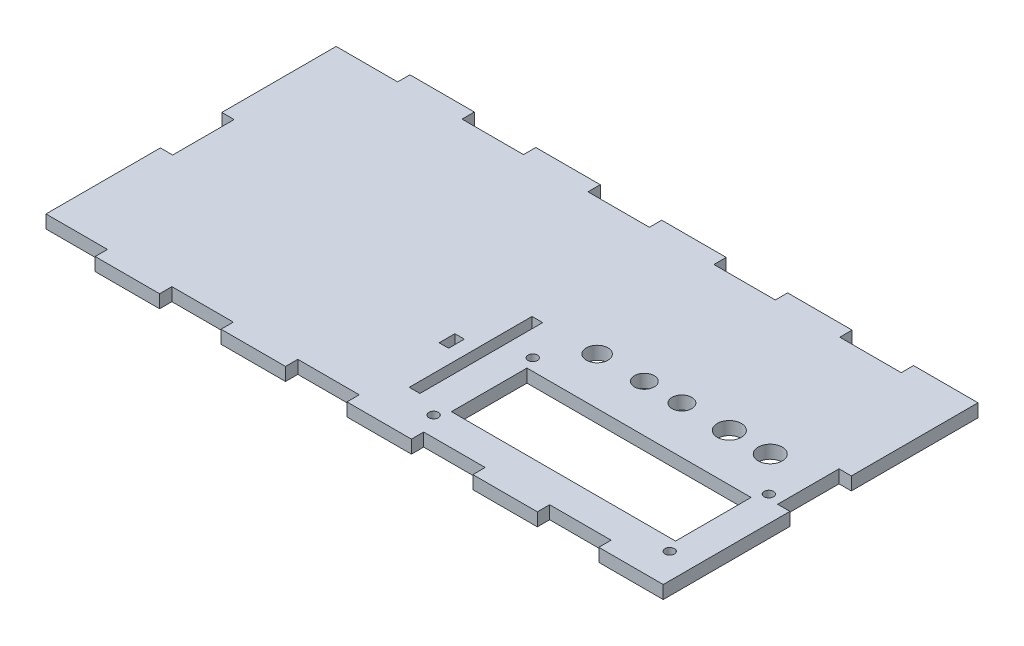
SolidWorks part; units mm, degrees
ref_plane "Front Plane" through (0, 0, 0) normal (0, 0, 1) x (1, 0, 0)
ref_plane "Top Plane" through (0, 0, 0) normal (0, 1, 0) x (1, 0, 0)
ref_plane "Right Plane" through (0, 0, 0) normal (1, 0, 0) x (0, 0, -1)
sketch "Sketch1" plane through (0, 0, 0) normal (0, 1, 0) x (1, 0, 0)
  line L1 (-100, 50) -> (100, 50)
  line L2 (-100, 50) -> (-100, -50)
  line L3 (-100, -50) -> (100, -50)
  line L4 (100, 50) -> (100, -50)
  line L5 (-100, 50) -> (100, -50) construction
  line L6 (-100, -50) -> (100, 50) construction
  point P0 (0, 0)
  dimension "Length" = 200
  dimension "with" = 100
extrude "Boss-Extrude1" add sketch "Sketch1" along normal blind 4.15
sketch "Sketch3" plane through (0, 4.15, 0) normal (0, 1, 0) x (1, 0, 0)
  line L0 (-100, 46.09) -> (-100, 50)
  line L1 (-100, -50) -> (-80.48, -50)
  line L2 (-100, -50) -> (-100, -46.09)
  line L3 (-100, -46.09) -> (-80.48, -46.09)
  line L4 (-80.48, -50) -> (-80.48, -46.09)
  line L5 (-100, 46.09) -> (-80.48, 46.09)
  line L6 (-80.48, 46.09) -> (-80.48, 50)
  line L7 (-100, 50) -> (-80.48, 50)
  line L8 (-60, 46.09) -> (-60, 50)
  line L9 (-60, 46.09) -> (-40.48, 46.09)
  line L10 (-40.48, 46.09) -> (-40.48, 50)
  line L11 (-60, 50) -> (-40.48, 50)
  line L12 (-20, 46.09) -> (-20, 50)
  line L13 (-20, 46.09) -> (-0.48, 46.09)
  line L14 (-0.48, 46.09) -> (-0.48, 50)
  line L15 (-20, 50) -> (-0.48, 50)
  line L16 (20, 46.09) -> (20, 50)
  line L17 (20, 46.09) -> (39.52, 46.09)
  line L18 (39.52, 46.09) -> (39.52, 50)
  line L19 (20, 50) -> (39.52, 50)
  line L20 (60, 46.09) -> (60, 50)
  line L21 (60, 46.09) -> (79.52, 46.09)
  line L22 (79.52, 46.09) -> (79.52, 50)
  line L23 (60, 50) -> (79.52, 50)
  line L24 (-60, -50) -> (-60, -46.09)
  line L25 (-60, -50) -> (-40.48, -50)
  line L26 (-40.48, -50) -> (-40.48, -46.09)
  line L27 (-60, -46.09) -> (-40.48, -46.09)
  line L28 (-20, -50) -> (-20, -46.09)
  line L29 (-20, -50) -> (-0.48, -50)
  line L30 (-0.48, -50) -> (-0.48, -46.09)
  line L31 (-20, -46.09) -> (-0.48, -46.09)
  line L32 (20, -50) -> (20, -46.09)
  line L33 (20, -50) -> (39.52, -50)
  line L34 (39.52, -50) -> (39.52, -46.09)
  line L35 (20, -46.09) -> (39.52, -46.09)
  line L36 (60, -50) -> (60, -46.09)
  line L37 (60, -50) -> (79.52, -50)
  line L38 (79.52, -50) -> (79.52, -46.09)
  line L39 (60, -46.09) -> (79.52, -46.09)
  line L40 (-100, -50) -> (100, -50) construction
  line L41 (100, 50) -> (-100, 50) construction
  point P5 (-80.48, -48.045)
  dimension "D1" = 3.91
  dimension "D2" = 19.52
  dimension "D5" = 20.48
  dimension "D3" = 2
  dimension "D4" = 5
extrude "Cut-Extrude2" cut sketch "Sketch3" against normal blind 10
sketch "Sketch4" plane through (0, 4.15, 0) normal (0, 1, 0) x (1, 0, 0)
  line L0 (-100, 9.76) -> (-100, -9.76)
  line L1 (-100, 9.76) -> (-96.09, 9.76)
  line L2 (-100, -9.76) -> (-96.09, -9.76)
  line L3 (-96.09, 9.76) -> (-96.09, -9.76)
  line L4 (-100, 46.09) -> (-100, -46.09) construction
  line L5 (0, -2.2825) -> (0, 2.2825) construction
  line L6 (100, -9.76) -> (96.09, -9.76)
  line L7 (96.09, 9.76) -> (96.09, -9.76)
  line L8 (100, 9.76) -> (96.09, 9.76)
  line L9 (100, 9.76) -> (100, -9.76)
  point P6 (-100, 0)
  dimension "D1" = 19.52
  dimension "D2" = 3.91
extrude "Cut-Extrude3" cut sketch "Sketch4" against normal blind 10
sketch "Sketch5" [suppressed] plane through (0, 4.15, 0) normal (0, 1, 0) x (1, 0, 0)
  line L0 (100, -36.09) -> (100, -40)
  line L1 (100, -36.09) -> (80.48, -36.09)
  line L2 (100, -40) -> (80.48, -40)
  line L3 (80.48, -36.09) -> (80.48, -40)
  line L4 (100, -40) -> (100, -9.76) construction
  line L5 (60, -36.09) -> (60, -40)
  line L6 (60, -36.09) -> (40.48, -36.09)
  line L7 (40.48, -36.09) -> (40.48, -40)
  line L8 (60, -40) -> (40.48, -40)
  line L9 (20, -36.09) -> (20, -40)
  line L10 (20, -36.09) -> (0.48, -36.09)
  line L11 (0.48, -36.09) -> (0.48, -40)
  line L12 (20, -40) -> (0.48, -40)
  line L13 (-20, -36.09) -> (-20, -40)
  line L14 (-20, -36.09) -> (-39.52, -36.09)
  line L15 (-39.52, -36.09) -> (-39.52, -40)
  line L16 (-20, -40) -> (-39.52, -40)
  line L17 (-60, -36.09) -> (-60, -40)
  line L18 (-60, -36.09) -> (-79.52, -36.09)
  line L19 (-79.52, -36.09) -> (-79.52, -40)
  line L20 (-60, -40) -> (-79.52, -40)
  line L21 (60, 40) -> (60, 36.09)
  line L22 (60, 40) -> (40.48, 40)
  line L23 (40.48, 40) -> (40.48, 36.09)
  line L24 (60, 36.09) -> (40.48, 36.09)
  line L25 (20, 40) -> (20, 36.09)
  line L26 (20, 40) -> (0.48, 40)
  line L27 (0.48, 40) -> (0.48, 36.09)
  line L28 (20, 36.09) -> (0.48, 36.09)
  line L29 (-20, 40) -> (-20, 36.09)
  line L30 (-20, 40) -> (-39.52, 40)
  line L31 (-39.52, 40) -> (-39.52, 36.09)
  line L32 (-20, 36.09) -> (-39.52, 36.09)
  line L33 (-60, 40) -> (-60, 36.09)
  line L34 (-60, 40) -> (-79.52, 40)
  line L35 (-79.52, 40) -> (-79.52, 36.09)
  line L36 (-60, 36.09) -> (-79.52, 36.09)
  line L37 (100, 40) -> (100, 36.09)
  line L38 (100, 40) -> (80.48, 40)
  line L39 (80.48, 40) -> (80.48, 36.09)
  line L40 (100, 36.09) -> (80.48, 36.09)
  line L41 (100, 40) -> (-100, 40) construction
  point P9 (100, 38.045)
  point P46 (100, -38.045)
  dimension "D1" = 3.91
  dimension "D2" = 19.52
  dimension "D5" = 20.48
  dimension "D3" = 5
  dimension "D4" = 2
extrude "Cut-Extrude4" [suppressed] cut sketch "Sketch5" against normal blind 10
sketch "Sketch6" [suppressed] plane through (0, 4.15, 0) normal (0, 1, 0) x (1, 0, 0)
  line L4 (-2.2825, 0) -> (2.2825, 0) construction
  line L5 (-40, -50) -> (-10.24, -50)
  line L6 (-40, -50) -> (-40, -46.09)
  line L7 (-40, -46.09) -> (-10.24, -46.09)
  line L8 (-10.24, -50) -> (-10.24, -46.09)
  line L9 (40, -50) -> (10.24, -50)
  line L10 (40, -50) -> (40, -46.09)
  line L11 (40, -46.09) -> (10.24, -46.09)
  line L12 (10.24, -50) -> (10.24, -46.09)
  line L13 (-40, 46.09) -> (-10.24, 46.09)
  line L14 (-10.24, 50) -> (-10.24, 46.09)
  line L15 (-40, 50) -> (-10.24, 50)
  line L16 (-40, 50) -> (-40, 46.09)
  line L17 (40, 46.09) -> (10.24, 46.09)
  line L18 (10.24, 50) -> (10.24, 46.09)
  line L19 (40, 50) -> (10.24, 50)
  line L20 (40, 50) -> (40, 46.09)
  line L21 (0, -2.2825) -> (0, 2.2825) construction
  line L22 (40, -46.09) -> (36.09, -46.09)
  line L23 (40, -46.09) -> (40, -10.24)
  line L24 (40, -10.24) -> (36.09, -10.24)
  line L25 (36.09, -46.09) -> (36.09, -10.24)
  line L26 (40, 46.09) -> (36.09, 46.09)
  line L27 (40, 46.09) -> (40, 10.24)
  line L28 (40, 10.24) -> (36.09, 10.24)
  line L29 (36.09, 46.09) -> (36.09, 10.24)
  line L30 (-40, 10.24) -> (-36.09, 10.24)
  line L31 (-36.09, 46.09) -> (-36.09, 10.24)
  line L32 (-40, 46.09) -> (-36.09, 46.09)
  line L33 (-40, 46.09) -> (-40, 10.24)
  line L34 (-40, -10.24) -> (-36.09, -10.24)
  line L35 (-36.09, -46.09) -> (-36.09, -10.24)
  line L36 (-40, -46.09) -> (-36.09, -46.09)
  line L37 (-40, -46.09) -> (-40, -10.24)
  dimension "D1" = 20.48
  dimension "D2" = 3.91
  dimension "D4" = 29.76
  dimension "D5" = 3.91
  dimension "D6" = 3.91
  dimension "D7" = 20.48
extrude "Cut-Extrude5" [suppressed] cut sketch "Sketch6" against normal blind 10
sketch "Sketch7" plane through (0, 4.15, 0) normal (0, 1, 0) x (1, 0, 0)
  line L0 (39.52, -46.09) -> (20, -46.09) construction
  line L1 (18.8, -36.09) -> (90, -36.09)
  line L2 (18.8, -36.09) -> (18.8, -12.09)
  line L3 (18.8, -12.09) -> (90, -12.09)
  line L4 (90, -36.09) -> (90, -12.09)
  line L5 (100, -50) -> (100, -9.76) construction
  dimension "D1" = 71.2
  dimension "D2" = 24
  dimension "D3" = 10
  dimension "D4" = 10
extrude "Cut-Extrude6" cut sketch "Sketch7" against normal blind 10
sketch "Sketch8" plane through (0, 4.15, 0) normal (0, 1, 0) x (1, 0, 0)
  line L0 (18.8, -12.09) -> (18.8, -36.09) construction
  line L1 (90, -36.09) -> (90, -12.09) construction
  line L4 (90, -12.09) -> (18.8, -12.09) construction
  line L5 (18.8, -36.09) -> (90, -36.09) construction
  circle A0 centre (16.9, -39.84) radius 1.5
  circle A1 centre (16.9, -8.34) radius 1.5
  circle A2 centre (91.9, -8.34) radius 1.5
  circle A3 centre (91.9, -39.84) radius 1.5
  dimension "D1" = 2
  dimension "D3" = 3
  dimension "D7" = 1.9
  dimension "D4" = 3.75
  dimension "D5" = 3.75
  dimension "D6" = 1.9
  dimension "D2" = 2
extrude "Cut-Extrude7" cut sketch "Sketch8" against normal blind 10
sketch "Sketch9" plane through (0, 4.15, 0) normal (0, 1, 0) x (1, 0, 0)
  line L0 (-0.48, -46.09) -> (-20, -46.09) construction
  line L1 (8.8, -36.09) -> (5.4, -36.09)
  line L2 (8.8, -36.09) -> (8.8, 2.91)
  line L3 (8.8, 2.91) -> (5.4, 2.91)
  line L4 (5.4, -36.09) -> (5.4, 2.91)
  line L5 (18.8, -12.09) -> (18.8, -36.09) construction
  dimension "D1" = 3.4
  dimension "D2" = 39
  dimension "D3" = 10
  dimension "D4" = 10
extrude "Cut-Extrude8" cut sketch "Sketch9" against normal blind 10
sketch "Sketch10" plane through (0, 4.15, 0) normal (0, 1, 0) x (1, 0, 0)
  line L0 (90, -12.09) -> (18.8, -12.09) construction
  line L1 (96.09, 9.76) -> (96.09, -9.76) construction
  circle A0 centre (26.09, 2.91) radius 3.425
  dimension "D1" = 6.85
  dimension "D2" = 15
  dimension "D3" = 70
extrude "Cut-Extrude9" cut sketch "Sketch10" against normal blind 10 contours A0
sketch "Sketch11" plane through (0, 4.15, 0) normal (0, 1, 0) x (1, 0, 0)
  line L0 (90, -12.09) -> (18.8, -12.09) construction
  line L1 (96.09, 9.76) -> (96.09, -9.76) construction
  circle A0 centre (41.09, 2.91) radius 3.125
  circle A1 centre (53.0309, 2.91) radius 3.125
  dimension "D1" = 6.25
  dimension "D3" = 55
  dimension "D2" = 15
  dimension "D4" = 2
extrude "Cut-Extrude10" cut sketch "Sketch11" against normal blind 10
sketch "Sketch12" plane through (0, 4.15, 0) normal (0, 1, 0) x (1, 0, 0)
  line L0 (90, -12.09) -> (18.8, -12.09) construction
  line L1 (96.09, 9.76) -> (96.09, -9.76) construction
  circle A0 centre (68.09, 2.91) radius 3.825
  circle A1 centre (81.09, 2.91) radius 3.825
  dimension "D1" = 7.65
  dimension "D2" = 15
  dimension "D4" = 28
  dimension "D5" = 15
  dimension "D3" = 2
extrude "Cut-Extrude11" cut sketch "Sketch12" against normal blind 10
sketch "Sketch13" [suppressed] plane through (0, 4.15, 0) normal (0, 1, 0) x (1, 0, 0)
  line L0 (100, -50) -> (100, 50) construction
  line L1 (24.76, 50) -> (-24.76, 50)
  line L3 (24.76, 45.78) -> (-24.76, 45.78)
  line L4 (-24.76, 50) -> (-24.76, 45.78)
  line L5 (0, -2.2825) -> (0, 2.2825) construction
  line L6 (-100, 50) -> (-50.24, 50)
  line L8 (-95.78, 45.78) -> (-50.24, 45.78)
  line L9 (-50.24, 50) -> (-50.24, 45.78)
  line L10 (95.78, 45.78) -> (50.24, 45.78)
  line L11 (50.24, 50) -> (50.24, 45.78)
  line L12 (100, 50) -> (50.24, 50)
  line L14 (24.76, 50) -> (24.76, 45.78)
  line L15 (-100, 50) -> (-100, -50) construction
  line L21 (-100, -15.72) -> (-100, 15.72)
  line L22 (-100, 15.72) -> (-95.78, 15.72)
  line L23 (-95.78, -15.72) -> (-95.78, 15.72)
  line L24 (-2.2825, 0) -> (2.2825, 0) construction
  line L26 (-100, 50) -> (-100, 30.24)
  line L27 (-100, 30.24) -> (-95.78, 30.24)
  line L28 (-95.78, 45.78) -> (-95.78, 30.24)
  line L29 (-100, -15.72) -> (-95.78, -15.72)
  line L30 (-100, -30.24) -> (-95.78, -30.24)
  line L31 (-95.78, -50) -> (-95.78, -30.24)
  line L32 (-100, -50) -> (-95.78, -50)
  line L33 (-100, -50) -> (-100, -30.24)
  line L34 (100, 30.24) -> (95.78, 30.24)
  line L35 (95.78, 45.78) -> (95.78, 30.24)
  line L37 (100, 50) -> (100, 30.24)
  line L38 (100, -15.72) -> (100, 15.72)
  line L39 (100, 15.72) -> (95.78, 15.72)
  line L40 (95.78, -15.72) -> (95.78, 15.72)
  line L41 (100, -15.72) -> (95.78, -15.72)
  line L42 (100, -50) -> (100, -30.24)
  line L43 (100, -50) -> (95.78, -50)
  line L44 (95.78, -50) -> (95.78, -30.24)
  line L45 (100, -30.24) -> (95.78, -30.24)
  line L46 (-100, -50) -> (100, -50) construction
  line L47 (100, 50) -> (-100, 50) construction
  dimension "D1" = 4.22
  dimension "D2" = 49.76
  dimension "D3" = 25.48
  dimension "D4" = 4.22
  dimension "D5" = 19.76
  dimension "D6" = 4.22
  dimension "D7" = 4.22
  dimension "D8" = 14.52
  dimension "D9" = 31.44
extrude "Cut-Extrude12" [suppressed] cut sketch "Sketch13" against normal blind 10
sketch "Sketch14" [suppressed] plane through (0, 4.15, 0) normal (0, 1, 0) x (1, 0, 0)
  line L0 (95.78, -30.24) -> (95.78, -50) construction
  line L1 (-96.02, -50) -> (95.78, -50)
  line L2 (-96.02, -50) -> (-96.02, -45.78)
  line L3 (-96.02, -45.78) -> (95.78, -45.78)
  line L4 (95.78, -50) -> (95.78, -45.78)
  dimension "D1" = 4.22
extrude "Cut-Extrude13" [suppressed] cut sketch "Sketch14" against normal blind 10
sketch "Sketch15" [suppressed] plane through (0, 4.15, 0) normal (0, 1, 0) x (1, 0, 0)
  line L0 (10.24, 50) -> (-10.24, 50) construction
  line L1 (2.35, 30) -> (-1.63, 30)
  line L2 (2.35, 30) -> (2.35, 15.48)
  line L3 (2.35, 15.48) -> (-1.63, 15.48)
  line L4 (-1.63, 30) -> (-1.63, 15.48)
  line L5 (2.35, 30) -> (-1.63, 15.48) construction
  line L6 (2.35, 15.48) -> (-1.63, 30) construction
  line L7 (36.09, 46.09) -> (36.09, 10.24) construction
  line L9 (-2.2825, 0) -> (2.2825, 0) construction
  line L10 (2.35, -15.48) -> (-1.63, -15.48)
  line L11 (-1.63, -30) -> (-1.63, -15.48)
  line L12 (2.35, -30) -> (-1.63, -30)
  line L13 (2.35, -30) -> (2.35, -15.48)
  point P0 (0.36, 22.74)
  dimension "D1" = 20
  dimension "D2" = 14.52
  dimension "D3" = 33.74
  dimension "D4" = 3.98
extrude "Cut-Extrude14" [suppressed] cut sketch "Sketch15" against normal blind 10
sketch "Sketch16" [suppressed] plane through (0, 4.15, 0) normal (0, 1, 0) x (1, 0, 0)
  line L1 (-25.24, 2.195) -> (-50.48, 2.195)
  line L2 (-25.24, 2.195) -> (-25.24, -2.195)
  line L3 (-25.24, -2.195) -> (-50.48, -2.195)
  line L4 (-50.48, 2.195) -> (-50.48, -2.195)
  line L5 (-25.24, 2.195) -> (-50.48, -2.195) construction
  line L6 (-25.24, -2.195) -> (-50.48, 2.195) construction
  line L8 (0, -2.2825) -> (0, 2.2825) construction
  line L9 (25.24, -2.195) -> (50.48, -2.195)
  line L10 (50.48, 2.195) -> (50.48, -2.195)
  line L11 (25.24, 2.195) -> (50.48, 2.195)
  line L12 (25.24, 2.195) -> (25.24, -2.195)
  line L13 (-25.24, -36.09) -> (-25.24, 36.09) construction
  line L14 (-20, -36.09) -> (-39.52, -36.09) construction
  line L15 (-39.52, 36.09) -> (-20, 36.09) construction
  line L16 (-100, 40) -> (-100, 9.76) construction
  point P0 (-37.86, 0)
  point P5 (-25.24, 0)
  point P6 (-25.24, 0)
  point P7 (25.24, 0)
  dimension "D1" = 4.39
  dimension "D2" = 49.52
  dimension "D3" = 25.24
extrude "Cut-Extrude15" [suppressed] cut sketch "Sketch16" against normal blind 10
sketch "Sketch17" [suppressed] plane through (0, 4.15, 0) normal (0, 1, 0) x (1, 0, 0)
  line L1 (50.24, 45.78) -> (95.78, 45.78) construction
  line L2 (-24.76, 45.78) -> (24.76, 45.78) construction
  line L3 (95.78, 15.72) -> (95.78, -15.72) construction
  circle A0 centre (85.78, 10.48) radius 1.5
  circle A1 centre (34.98, 25.78) radius 1.5
  circle A2 centre (85.78, -17.42) radius 1.5
  circle A3 centre (33.38, -22.52) radius 1.5
  dimension "D7" = 3
  dimension "D8" = 3
  dimension "D9" = 3
  dimension "D10" = 3
  dimension "D11" = 10
  dimension "D12" = 10
  dimension "D1" = 35.3
  dimension "D2" = 20
  dimension "D3" = 50.8
  dimension "D4" = 27.9
  dimension "D5" = 52.4
  dimension "D6" = 48.3
extrude "Cut-Extrude16" [suppressed] cut sketch "Sketch17" against normal blind 10
sketch "Sketch18" [suppressed] plane through (0, 4.15, 0) normal (0, 1, 0) x (1, 0, 0)
  line L0 (95.78, 15.72) -> (95.78, -15.72) construction
  line L1 (7.78, 37.5) -> (27.78, 37.5)
  line L2 (7.78, 37.5) -> (7.78, -5)
  line L3 (7.78, -37.5) -> (27.78, -37.5)
  line L4 (27.78, 37.5) -> (27.78, -37.5)
  line L8 (7.78, -37.5) -> (-7.22, -37.5)
  line L10 (95.78, -45.78) -> (-95.78, -45.78) construction
  line L11 (-24.76, 45.78) -> (24.76, 45.78) construction
  line L12 (7.78, -5) -> (-7.22, -5)
  line L13 (-7.22, -37.5) -> (-7.22, -5)
  dimension "D1" = 20
  dimension "D2" = 8.28
  dimension "D3" = 68
  dimension "D4" = 8.28
  dimension "D5" = 5
  dimension "D6" = 15
extrude "Cut-Extrude18" [suppressed] cut sketch "Sketch18" against normal blind 10
sketch "Sketch19" plane through (0, 4.15, 0) normal (0, 1, 0) x (1, 0, 0)
  line L0 (5.4, 2.91) -> (5.4, -36.09) construction
  line L1 (-2.1, -14.09) -> (0.9, -14.09)
  line L2 (-2.1, -14.09) -> (-2.1, -19.09)
  line L3 (-2.1, -19.09) -> (0.9, -19.09)
  line L4 (0.9, -14.09) -> (0.9, -19.09)
  line L5 (-2.1, -14.09) -> (0.9, -19.09) construction
  line L6 (-2.1, -19.09) -> (0.9, -14.09) construction
  point P0 (-0.6, -16.59)
  point P7 (5.4, -16.59)
  point P8 (0.9, -16.59)
  dimension "D1" = 4.5
  dimension "D2" = 3
  dimension "D4" = 5
extrude "Cut-Extrude19" cut sketch "Sketch19" against normal blind 4.2
sketch "Sketch20" [suppressed] plane through (0, 4.15, 0) normal (0, 1, 0) x (1, 0, 0)
  line L0 (100, -30.24) -> (100, -15.72) construction
  line L1 (-1.85, -18.28) -> (1.15, -18.28)
  line L2 (-1.85, -18.28) -> (-1.85, -23.28)
  line L3 (-1.85, -23.28) -> (1.15, -23.28)
  line L4 (1.15, -18.28) -> (1.15, -23.28)
  line L5 (-1.85, -18.28) -> (1.15, -23.28) construction
  line L6 (-1.85, -23.28) -> (1.15, -18.28) construction
  line L8 (95.78, -45.78) -> (-95.78, -45.78) construction
  point P0 (-0.35, -20.78)
  dimension "D1" = 22.5
  dimension "D2" = 98.85
  dimension "D3" = 3
  dimension "D4" = 5
extrude "Cut-Extrude21" [suppressed] cut sketch "Sketch20" against normal blind 4.2
sketch "Sketch21" [suppressed] plane through (0, 4.15, 0) normal (0, 1, 0) x (1, 0, 0)
  line L0 (100, 9.76) -> (100, 50) construction
  line L1 (-1.85, -18.59) -> (1.15, -18.59)
  line L2 (-1.85, -18.59) -> (-1.85, -23.59)
  line L3 (-1.85, -23.59) -> (1.15, -23.59)
  line L4 (1.15, -18.59) -> (1.15, -23.59)
  line L5 (-1.85, -18.59) -> (1.15, -23.59) construction
  line L6 (-1.85, -23.59) -> (1.15, -18.59) construction
  line L8 (-0.48, -46.09) -> (-20, -46.09) construction
  point P0 (-0.35, -21.09)
  dimension "D1" = 3
  dimension "D2" = 5
  dimension "D3" = 98.85
  dimension "D4" = 22.5
extrude "Cut-Extrude22" [suppressed] cut sketch "Sketch21" against normal blind 4.2
equation "\"kerf\"=0.24"
equation "\"D5@Sketch5\"=20 + 2*\"kerf\""
